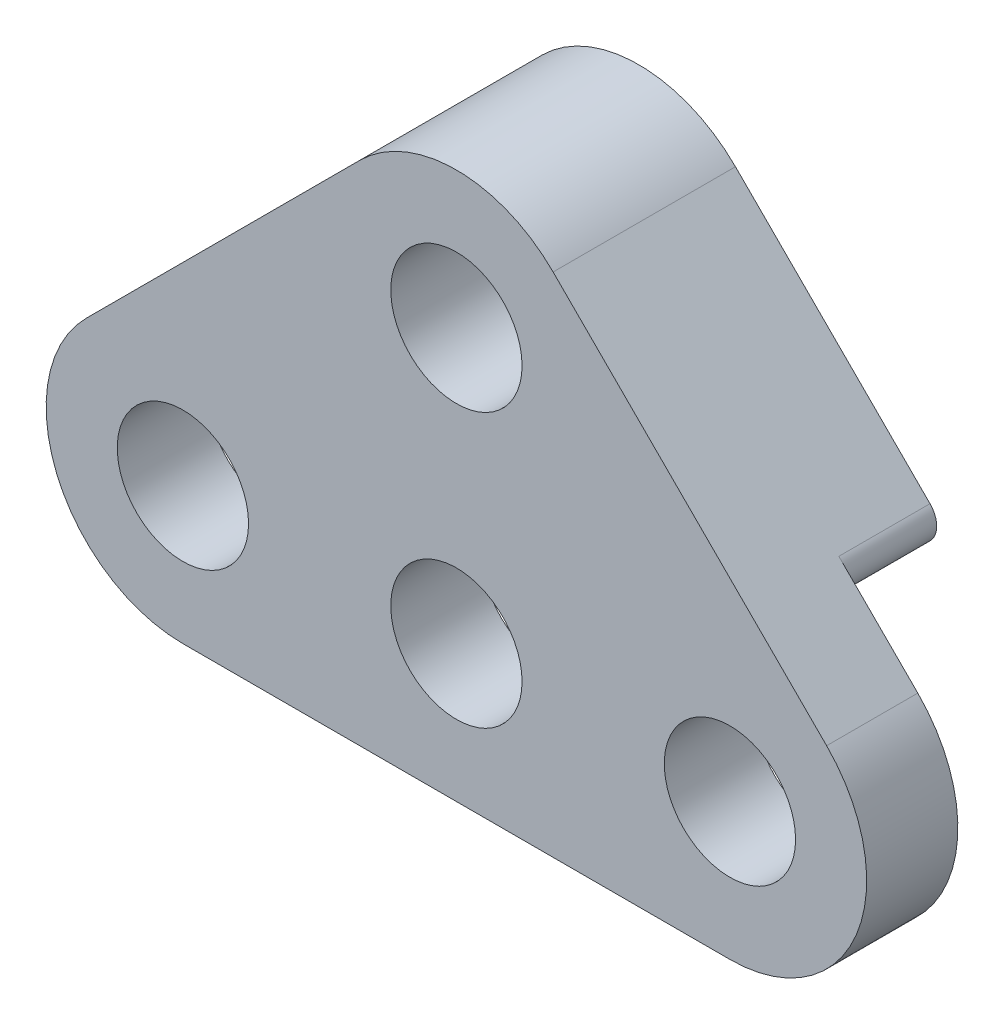
SolidWorks part; units mm, degrees
ref_plane "Front" through (0, 0, 0) normal (0, 0, 1) x (1, 0, 0)
ref_plane "Top" through (0, 0, 0) normal (0, 1, 0) x (1, 0, 0)
ref_plane "Right" through (0, 0, 0) normal (1, 0, 0) x (0, 0, -1)
sketch "Sketch1" plane through (0, 0, 0) normal (0, 0, 1) x (1, 0, 0)
  line L0 (-9.525, 0) -> (9.525, 0) construction
  line L1 (55, 0) -> (-55, 0) construction
  line L2 (-12.8926, 3.3676) -> (-3.3676, 12.8926)
  line L3 (12.8926, 3.3676) -> (3.3676, 12.8926)
  line L4 (-9.525, -4.7625) -> (9.525, -4.7625)
  line L5 (-11.4977, 4.7625) -> (11.4977, 4.7625)
  circle A0 centre (0, 0) radius 2.286
  circle A1 centre (-9.525, 0) radius 2.286
  circle A2 centre (9.525, 0) radius 2.286
  circle A3 centre (0, 9.525) radius 2.286
  arc A4 (3.3676, 12.8926) -> (-3.3676, 12.8926) centre (0, 9.525) ccw
  arc A5 (-12.8926, 3.3676) -> (-9.525, -4.7625) centre (-9.525, 0) ccw
  arc A6 (9.525, -4.7625) -> (12.8926, 3.3676) centre (9.525, 0) ccw
  point P8 (0, 0)
  dimension "D1" = 4.572
  dimension "D5" = 9.525
  dimension "D2" = 19.05
  dimension "D3" = 9.525
  dimension "D4" = 9.525
extrude "Boss-Extrude1" add sketch "Sketch1" along normal blind 3.175 contours A6 L5 A5 L4 A1 A0 A2 | A6 L3 A4 L2 A5 L5 A3 region at (-11.9822, 3.8521, 0) region at (-7.2566, 8.6515, 0)
extrude "Boss-Extrude2" add sketch "Sketch1<4>" against normal blind 3.175 contours L3 A4 L2 L5 A3 region at (-7.2566, 8.6515, 0)
sketch "Sketch1<4>" plane through (0, 0, 0) normal (0, 0, 1) x (1, 0, 0) same geometry as "Sketch1"
fillet "Fillet1" radius 0.7937 2 edges at (-11.4977, 4.7625, -1.5875) (11.4977, 4.7625, -1.5875)
